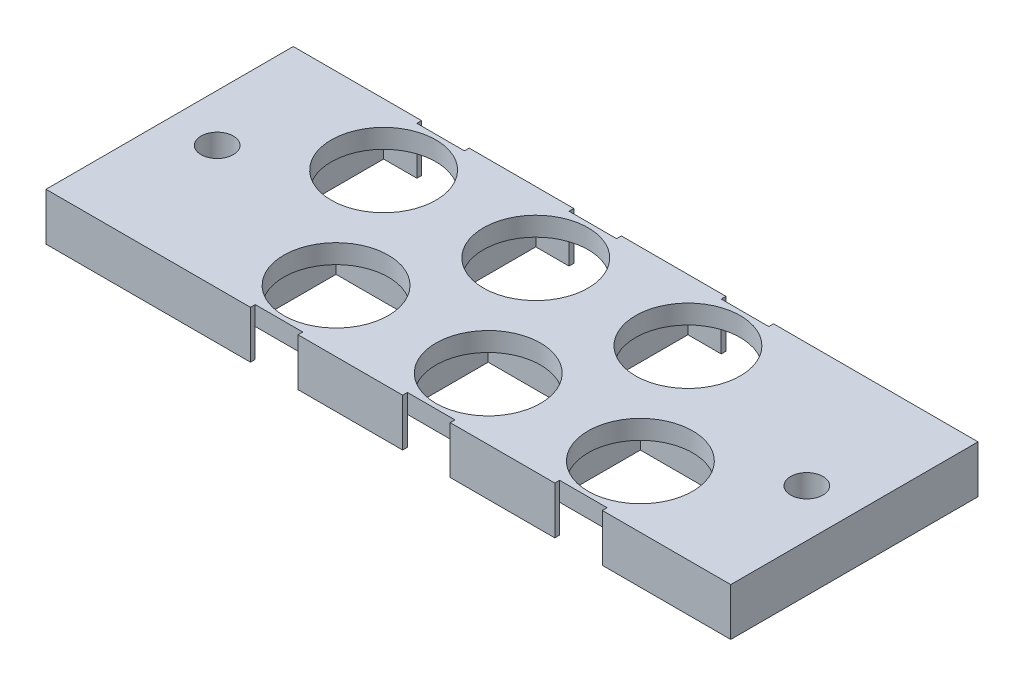
SolidWorks part; units mm, degrees
ref_plane "Front Plane" through (0, 0, 0) normal (0, 0, 1) x (1, 0, 0)
ref_plane "Top Plane" through (0, 0, 0) normal (0, 1, 0) x (1, 0, 0)
ref_plane "Right Plane" through (0, 0, 0) normal (1, 0, 0) x (0, 0, -1)
sketch "Sketch1" plane through (0, 0, 0) normal (0, 1, 0) x (1, 0, 0)
  line L0 (3.1864, -4.1649) -> (6.1864, -4.1649)
  line L1 (19.1864, -4.1649) -> (22.1864, -4.1649)
  line L2 (27.1864, -30.1649) -> (30.1864, -30.1649)
  line L3 (11.1864, -30.1649) -> (14.1864, -30.1649)
  line L4 (43.1864, -30.1649) -> (52.6864, -30.1649)
  line L5 (52.6864, -30.1649) -> (52.6864, -4.1649)
  line L6 (52.6864, -4.1649) -> (35.1864, -4.1649)
  line L7 (-9.8136, -4.1649) -> (-19.3136, -4.1649)
  line L8 (-19.3136, -4.1649) -> (-19.3136, -30.1649)
  line L9 (-19.3136, -30.1649) -> (-1.8136, -30.1649)
  line L10 (-14.3136, -4.1649) -> (-14.3136, -30.1649) construction
  line L11 (47.6864, -4.1649) -> (47.6864, -30.1649) construction
  circle A0 centre (-14.3136, -17.1649) radius 1.7
  circle A1 centre (47.6864, -17.1649) radius 1.7
  line B0 (35.1864, -17.1649) -> (35.1864, -4.1649)
  line B1 (11.1864, -30.1649) -> (7.1864, -30.1649)
  line B2 (-1.3136, -29.6649) -> (10.6864, -29.6649)
  line B3 (11.1864, -30.1649) -> (11.1864, -17.1649)
  line B4 (27.1864, -30.1649) -> (27.1864, -17.1649)
  line B5 (43.1864, -30.1649) -> (43.1864, -17.1649)
  line B6 (-1.8136, -17.1649) -> (-1.8136, -30.1649)
  line B7 (10.6864, -29.6649) -> (10.6864, -17.6649)
  line B8 (30.1864, -17.1649) -> (30.1864, -30.1649)
  line B9 (22.1864, -4.1649) -> (22.1864, -17.1649)
  line B10 (34.6864, -16.6649) -> (34.6864, -4.6649)
  line B11 (18.6864, -16.6649) -> (18.6864, -4.6649)
  line B12 (3.1864, -17.1649) -> (3.1864, -4.1649)
  line B13 (42.6864, -29.6649) -> (42.6864, -17.6649)
  line B14 (14.6864, -29.6649) -> (26.6864, -29.6649)
  line B15 (30.6864, -17.6649) -> (30.6864, -29.6649)
  line B16 (30.6864, -17.6649) -> (42.6864, -29.6649) construction
  line B17 (14.6864, -17.6649) -> (26.6864, -29.6649) construction
  line B18 (-1.3136, -17.6649) -> (10.6864, -29.6649) construction
  line B19 (43.1864, -17.1649) -> (30.1864, -17.1649)
  line B20 (2.6864, -16.6649) -> (2.6864, -4.6649)
  line B21 (14.6864, -17.6649) -> (14.6864, -29.6649)
  line B22 (27.1864, -30.1649) -> (23.1864, -30.1649)
  line B23 (30.1864, -30.1649) -> (34.1864, -30.1649)
  line B24 (43.1864, -30.1649) -> (39.1864, -30.1649)
  line B25 (-9.3136, -10.6649) -> (2.6864, -10.6649) construction
  line B26 (6.6864, -10.6649) -> (18.6864, -10.6649) construction
  line B27 (22.6864, -10.6649) -> (34.6864, -10.6649) construction
  line B28 (-1.3136, -23.6649) -> (10.6864, -23.6649) construction
  line B29 (14.6864, -23.6649) -> (26.6864, -23.6649) construction
  line B30 (30.6864, -23.6649) -> (42.6864, -23.6649) construction
  line B31 (-27.4152, -23.6649) -> (51.2342, -23.6649) construction
  line B32 (22.1864, -17.1649) -> (35.1864, -17.1649)
  line B33 (-27.4152, -10.6649) -> (51.2342, -10.6649) construction
  line B34 (28.6864, -16.6649) -> (28.6864, -4.6649) construction
  line B35 (36.6864, -17.6649) -> (36.6864, -29.6649) construction
  line B36 (20.6864, -17.6649) -> (20.6864, -29.6649) construction
  line B37 (12.6864, -16.6649) -> (12.6864, -4.6649) construction
  line B38 (4.6864, -17.6649) -> (4.6864, -29.6649) construction
  line B39 (-3.3136, -16.6649) -> (-3.3136, -4.6649) construction
  line B40 (22.6864, -4.6649) -> (22.6864, -16.6649)
  line B41 (22.6864, -16.6649) -> (34.6864, -16.6649)
  line B42 (34.6864, -4.6649) -> (22.6864, -4.6649)
  line B43 (34.6864, -16.6649) -> (22.6864, -4.6649) construction
  line B44 (34.6864, -4.6649) -> (22.6864, -16.6649) construction
  line B45 (35.1864, -4.1649) -> (31.1864, -4.1649)
  line B46 (22.1864, -4.1649) -> (26.1864, -4.1649)
  line B47 (31.1864, -4.1649) -> (31.1864, -4.6649)
  line B48 (26.1864, -4.1649) -> (26.1864, -4.6649)
  circle B49 centre (28.6864, -10.6649) radius 5.5
  line B50 (-1.3136, -17.6649) -> (-1.3136, -29.6649)
  line B51 (10.6864, -17.6649) -> (-1.3136, -17.6649)
  line B52 (-1.3136, -29.6649) -> (10.6864, -17.6649) construction
  line B53 (11.1864, -17.1649) -> (-1.8136, -17.1649)
  line B54 (-1.8136, -30.1649) -> (2.1864, -30.1649)
  line B55 (2.1864, -30.1649) -> (2.1864, -29.6649)
  line B56 (7.1864, -30.1649) -> (7.1864, -29.6649)
  circle B57 centre (4.6864, -23.6649) radius 5.5
  line B58 (26.6864, -29.6649) -> (26.6864, -17.6649)
  line B59 (26.6864, -17.6649) -> (14.6864, -17.6649)
  line B60 (14.6864, -29.6649) -> (26.6864, -17.6649) construction
  line B61 (27.1864, -17.1649) -> (14.1864, -17.1649)
  line B62 (14.1864, -17.1649) -> (14.1864, -30.1649)
  line B63 (14.1864, -30.1649) -> (18.1864, -30.1649)
  line B64 (18.1864, -30.1649) -> (18.1864, -29.6649)
  line B65 (23.1864, -30.1649) -> (23.1864, -29.6649)
  circle B66 centre (20.6864, -23.6649) radius 5.5
  line B67 (42.6864, -17.6649) -> (30.6864, -17.6649)
  line B68 (30.6864, -29.6649) -> (42.6864, -29.6649)
  line B69 (30.6864, -29.6649) -> (42.6864, -17.6649) construction
  line B70 (34.1864, -30.1649) -> (34.1864, -29.6649)
  line B71 (39.1864, -30.1649) -> (39.1864, -29.6649)
  circle B72 centre (36.6864, -23.6649) radius 5.5
  line B73 (6.6864, -4.6649) -> (6.6864, -16.6649)
  line B74 (6.6864, -16.6649) -> (18.6864, -16.6649)
  line B75 (18.6864, -4.6649) -> (6.6864, -4.6649)
  line B76 (18.6864, -16.6649) -> (6.6864, -4.6649) construction
  line B77 (18.6864, -4.6649) -> (6.6864, -16.6649) construction
  line B78 (6.1864, -17.1649) -> (19.1864, -17.1649)
  line B79 (19.1864, -17.1649) -> (19.1864, -4.1649)
  line B80 (6.1864, -4.1649) -> (6.1864, -17.1649)
  line B81 (19.1864, -4.1649) -> (15.1864, -4.1649)
  line B82 (6.1864, -4.1649) -> (10.1864, -4.1649)
  line B83 (15.1864, -4.1649) -> (15.1864, -4.6649)
  line B84 (10.1864, -4.1649) -> (10.1864, -4.6649)
  circle B85 centre (12.6864, -10.6649) radius 5.5
  line B86 (-9.3136, -4.6649) -> (-9.3136, -16.6649)
  line B87 (-9.3136, -16.6649) -> (2.6864, -16.6649)
  line B88 (2.6864, -4.6649) -> (-9.3136, -4.6649)
  line B89 (2.6864, -16.6649) -> (-9.3136, -4.6649) construction
  line B90 (2.6864, -4.6649) -> (-9.3136, -16.6649) construction
  line B91 (-9.8136, -17.1649) -> (3.1864, -17.1649)
  line B92 (-9.8136, -4.1649) -> (-9.8136, -17.1649)
  line B93 (3.1864, -4.1649) -> (-0.8136, -4.1649)
  line B94 (-9.8136, -4.1649) -> (-5.8136, -4.1649)
  line B95 (-0.8136, -4.1649) -> (-0.8136, -4.6649)
  line B96 (-5.8136, -4.1649) -> (-5.8136, -4.6649)
  circle B97 centre (-3.3136, -10.6649) radius 5.5
  dimension "D1" = 9.5
  dimension "D2" = 9.5
  dimension "D3" = 72
  dimension "D4" = 5
  dimension "D5" = 5
sketch_block_instance "Block1-5"
sketch_block "Block1" parameters "D3"=6, "D1"=12, "D2"=12, "D4"=12, "D5"=78.6494, "D6"=78.6494, "D7"=78.6494, "D8"=10.3235, "D9"=14.0261, "D10"=17.7654, "D11"=23.7534, "D12"=22.7743, "D13"=52
sketch_block_instance "Block2-2"
sketch_block "Block2" parameters "D2"=8, "D1"=12
sketch_block_instance "Block2-3"
sketch_block_instance "Block2-4"
sketch_block_instance "Block2-5"
sketch_block_instance "Block2-6"
sketch_block_instance "Block2-7"
sketch_block_instance "Block3-1"
sketch_block "Block3"
sketch_block_instance "Block4-1"
sketch_block "Block4"
sketch_block_instance "Block5-1"
sketch_block "Block5"
sketch_block_instance "Block6-1"
sketch_block "Block6"
sketch_block_instance "Block7-1"
sketch_block "Block7"
sketch_block_instance "Block8-1"
sketch_block "Block8"
extrude "Boss-Extrude1" add sketch "Sketch1" against normal blind 2 contours B20 B88 B86 B87 B97 | B11 B75 B73 B74 B85 | B10 B42 B40 B41 B49 | B21 B14 B58 B59 B66 | B50 B2 B7 B51 B57 | B15 B68 B13 B67 B72 region at (0.9364, 0, 4.8346) region at (12.6864, 0, 4.8346) region at (0.4364, 0, 29.4952) region at (16.4364, 0, 29.4952) region at (28.6864, 0, 4.8346) region at (32.4364, 0, 29.4952)
extrude "Boss-Extrude2" add sketch "Sketch1<3>" against normal blind 5 contours B5 L4 L5 L6 B0 B19 A1 | B92 L7 L8 L9 B6 B91 A0 | B12 B53 B80 L0 | B78 B3 L3 B62 | B8 B32 B4 L2 | B71 B24 B5 B19 B32 B8 B23 B70 B68 B15 B67 B13 | B65 B22 B4 B32 B61 B62 B63 B64 B14 B21 B59 B58 | B96 B94 B92 B91 B53 B12 B93 B95 B88 B20 B87 B86 | B84 B82 B80 B53 B78 B61 B79 B81 B83 B75 B11 B74 B73 | B79 B61 B9 L1 | B48 B46 B9 B32 B0 B45 B47 B42 B10 B41 B40 | B56 B1 B3 B53 B6 B54 B55 B2 B50 B51 B7 region at (4.6864, 0, 10.6649) region at (3.0025, 0, 10.6649) region at (8.1864, 0, 4.3487) region at (4.6864, 0, 17.3487) region at (-11.9088, 0, 19.1419) region at (12.6864, 0, 23.6649) region at (16.6864, 0, 17.3487) region at (20.6864, 0, 10.6649) region at (22.3702, 0, 10.6649) region at (28.6864, 0, 23.6649) region at (32.6864, 0, 17.3487) region at (45.2816, 0, 15.1878)
sketch "Sketch1<3>" plane through (0, 0, 0) normal (0, 1, 0) x (1, 0, 0) same geometry as "Sketch1"
sketch "Sketch2" plane through (0, -5, 0) normal (0, -1, 0) x (-1, 0, 0)
  text T0 "F6"
extrude "Cut-Extrude1" cut sketch "Sketch2" against normal blind 1
